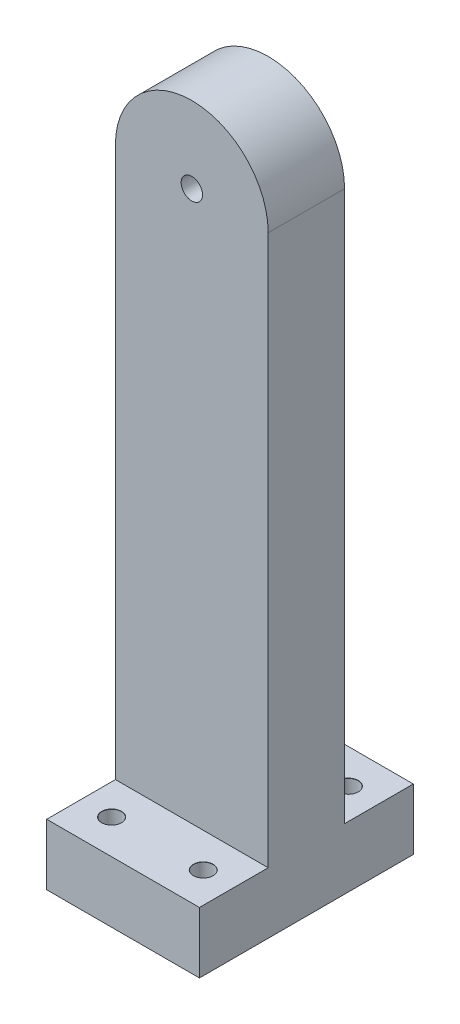
SolidWorks part; units mm, degrees
ref_plane "Front Plane" through (0, 0, 0) normal (0, 0, 1) x (1, 0, 0)
ref_plane "Top Plane" through (0, 0, 0) normal (0, 1, 0) x (1, 0, 0)
ref_plane "Right Plane" through (0, 0, 0) normal (1, 0, 0) x (0, 0, -1)
sketch "Sketch1" plane through (0, 0, 0) normal (0, 0, 1) x (1, 0, 0)
  line L0 (0, 0) -> (-12.5, 0)
  line L1 (-12.5, 0) -> (-12.5, 100)
  line L3 (12.5, 100) -> (12.5, 0)
  line L4 (12.5, 0) -> (0, 0)
  line L5 (0, 0) -> (0, 100) construction
  arc A0 (-12.5, 100) -> (12.5, 100) centre (0, 100) cw
  circle A1 centre (0, 100) radius 1.75
  dimension "D5" = 3.5
  dimension "D1" = 25
  dimension "D2" = 100
extrude "Boss-Extrude1" add sketch "Sketch1" along normal blind 35
sketch "Sketch5" plane through (12.5, 0, 0) normal (1, 0, 0) x (0, 0, -1)
  line L0 (-35, 0) -> (-35, 100) construction
  line L1 (-35, 10) -> (-23.75, 10)
  line L2 (-35, 10) -> (-35, 112.5)
  line L3 (-35, 112.5) -> (-23.75, 112.5)
  line L4 (-23.75, 10) -> (-23.75, 112.5)
  line L5 (0, 112.5) -> (-35, 112.5) construction
  line L6 (-35, 0) -> (0, 0) construction
  line L8 (0, 0) -> (0, 100) construction
  line L9 (0, 10) -> (-11.25, 10)
  line L10 (0, 10) -> (0, 112.5)
  line L11 (0, 112.5) -> (-11.25, 112.5)
  line L12 (-11.25, 10) -> (-11.25, 112.5)
  dimension "D1" = 10
  dimension "D2" = 12.5
extrude "Cut-Extrude1" cut sketch "Sketch5" against normal through all
sketch "Sketch9" plane through (0, 10, 0) normal (0, 1, 0) x (1, 0, 0)
  line L0 (0, 0) -> (0, -35) construction
  line L1 (-12.5, -35) -> (12.5, -35) construction
  line L3 (-12.5, -29.375) -> (12.5, -29.375) construction
  line L4 (-12.5, -35) -> (-12.5, -23.75) construction
  line L5 (12.5, -35) -> (12.5, -23.75) construction
  line L7 (-12.5, -5.625) -> (12.5, -5.625) construction
  line L8 (-12.5, -11.25) -> (-12.5, 0) construction
  line L9 (12.5, -11.25) -> (12.5, 0) construction
  point P0 (-7.5, -5.625)
  point P2 (7.5, -5.625)
  point P4 (7.5, -29.375)
  point P6 (-7.5, -29.375)
  point P35 (0, 0)
  point P36 (0, 0)
  dimension "D1" = 15
hole_wizard "Ø3.2 (3.2) Diameter Hole1" positions "Sketch9" profile "Sketch8" hole size "Ø3.2" standard "ANSI Metric" end condition through all
sketch "Sketch8" plane through (-7.5, 10, 5.625) normal (1, 0, 0) x (0, 0, 1)
  line L0 (0, 0) -> (0, 10)
  line L1 (0, 10) -> (1.6, 10)
  line L2 (1.6, 10) -> (1.6, 0.025)
  line L3 (1.6, 0.025) -> (1.625, 0)
  line L5 (1.625, 0) -> (0, 0)
  line L6 (-1.6, 0.025) -> (-1.625, 0) construction
  line L11 (0, -6.35) -> (0, 107.95) construction
  dimension "Thru Hole Dia." = 3.2
  dimension "Thru Hole Depth" = 10
  dimension "Near C'Sink Dia." = 3.25
  dimension "Near C'Sink Angle" = 90
